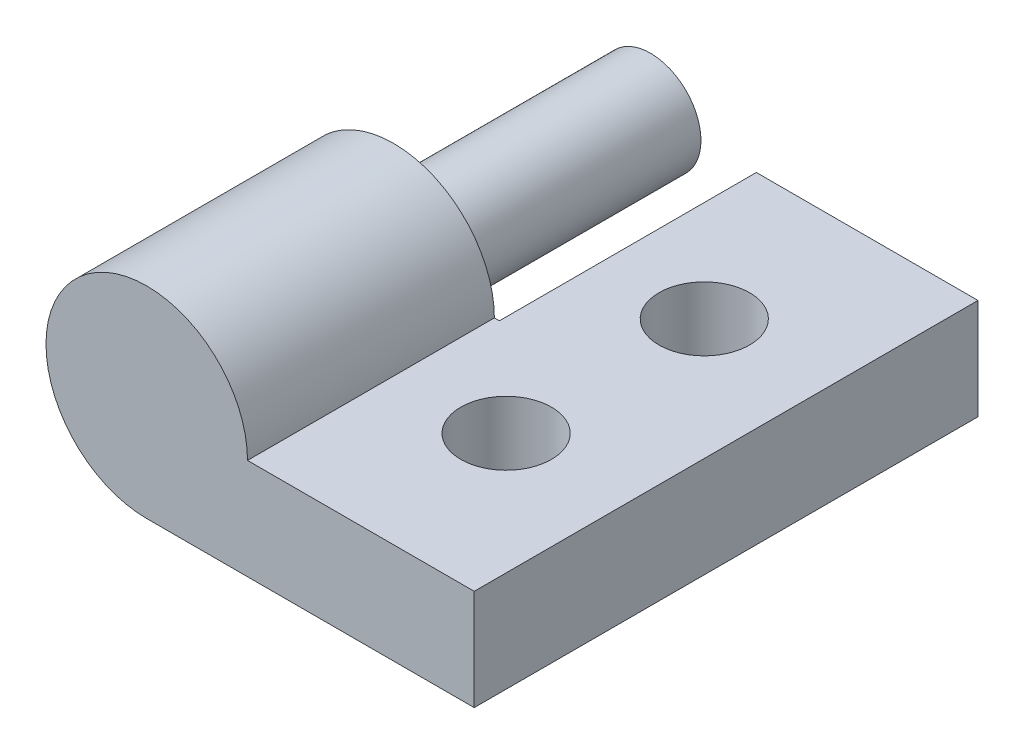
SolidWorks part; units mm, degrees
ref_plane "Front Plane" through (0, 0, 0) normal (0, 0, 1) x (1, 0, 0)
ref_plane "Top Plane" through (0, 0, 0) normal (0, 1, 0) x (1, 0, 0)
ref_plane "Right Plane" through (0, 0, 0) normal (1, 0, 0) x (0, 0, -1)
sketch "Sketch2" plane through (0, 0, 0) normal (0, 0, 1) x (1, 0, 0)
  line L1 (0, 0) -> (-16.51, 0)
  line L2 (0, 0) -> (0, 5.08)
  line L3 (0, 5.08) -> (-11.43, 5.08)
  arc A0 (-11.43, 5.08) -> (-16.51, 0) centre (-16.51, 5.08) ccw
  dimension "D3" = 5.08
  dimension "D1" = 16.51
  dimension "D2" = 5.08
extrude "Boss-Extrude1" add sketch "Sketch2" along normal blind 25.4
sketch "Sketch5" plane through (0, 5.08, 0) normal (0, 1, 0) x (1, 0, 0)
  line L0 (-6.096, -15.4093) -> (-6.096, -9.9907) construction
  line L1 (-6.096, -19.9813) -> (-6.096, -25.4) construction
  line L2 (0, -25.4) -> (-11.43, -25.4) construction
  line L3 (-6.096, -5.4187) -> (-6.096, 0) construction
  line L4 (0, 0) -> (-11.43, 0) construction
  line L5 (-6.096, -7.7047) -> (-16.51, -7.7047) construction
  line L9 (-16.51, -25.4) -> (-16.51, 0) construction
  circle A0 centre (-6.096, -17.6953) radius 2.286
  circle A1 centre (-6.096, -7.7047) radius 2.286
  dimension "D1" = 4.572
  dimension "D2" = 4.572
  dimension "D3" = 10.414
extrude "Cut-Extrude3" cut sketch "Sketch5" against normal blind 12.954
sketch "Sketch8" plane through (0, 0, 0) normal (0, 0, -1) x (-1, 0, 0)
  circle A0 centre (19.3527, 9.2811) radius 0.0075
  circle A1 centre (16.51, 5.08) radius 5.08
  circle A2 centre (16.51, 5.08) radius 5.334
  dimension "D1" = 10.668
extrude "Cut-Extrude5" cut sketch "Sketch8" against normal blind 12.954 contours A2
sketch "Sketch9" plane through (0, 0, 12.954) normal (0, 0, -1) x (-1, 0, 0)
  circle A0 centre (16.51, 5.08) radius 5.08
  circle A1 centre (16.51, 5.08) radius 2.54
  dimension "D1" = 5.08
extrude "Boss-Extrude2" add sketch "Sketch9" along normal blind 12.954 contours A1
